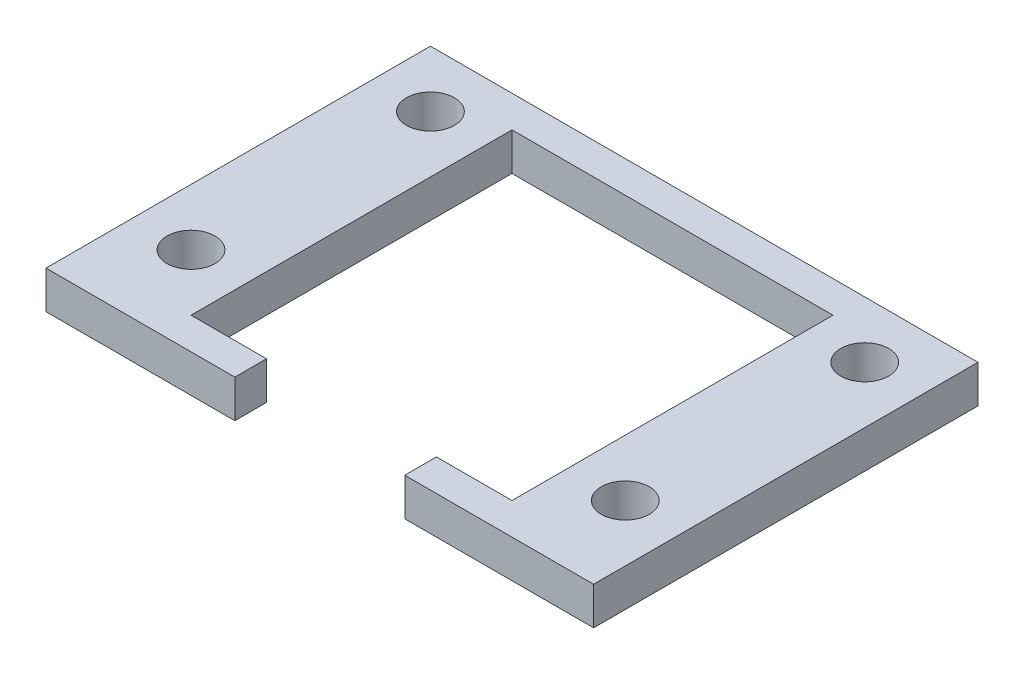
SolidWorks part; units mm, degrees
ref_plane "Front Plane" through (0, 0, 0) normal (0, 0, 1) x (1, 0, 0)
ref_plane "Top Plane" through (0, 0, 0) normal (0, 1, 0) x (1, 0, 0)
ref_plane "Right Plane" through (0, 0, 0) normal (1, 0, 0) x (0, 0, -1)
sketch "Sketch1" plane through (0, 0, 0) normal (0, 1, 0) x (1, 0, 0)
  line L1 (0, 0) -> (42.5, 0)
  line L2 (0, 0) -> (0, 42.5)
  line L3 (0, 42.5) -> (42.5, 42.5)
  line L4 (42.5, 0) -> (42.5, 42.5)
  line L5 (-15, 0) -> (57.5, 0)
  line L6 (-15, 0) -> (-15, 46.7)
  line L7 (-15, 46.7) -> (57.5, 46.7)
  line L8 (57.5, 0) -> (57.5, 46.7)
  line L9 (-15, 0) -> (10, 0)
  line L10 (-15, 0) -> (-15, -4.2)
  line L11 (-15, -4.2) -> (10, -4.2)
  line L12 (10, 0) -> (10, -4.2)
  line L13 (57.5, 0) -> (32.5, 0)
  line L14 (57.5, 0) -> (57.5, -4.2)
  line L15 (57.5, -4.2) -> (32.5, -4.2)
  line L16 (32.5, 0) -> (32.5, -4.2)
  circle A0 centre (-7.5, 7.5) radius 3.175
  circle A1 centre (-7.5, 39.2) radius 3.175
  circle A2 centre (50, 39.2) radius 3.175
  circle A3 centre (50, 7.5) radius 3.175
  dimension "D5" = 6.35
  dimension "D1" = 42.5
  dimension "D2" = 15
  dimension "D3" = 15
  dimension "D4" = 4.2
  dimension "D6" = 7.5
  dimension "D7" = 7.5
  dimension "D8" = 7.5
  dimension "D9" = 7.5
  dimension "D10" = 4.2
  dimension "D11" = 10
extrude "Boss-Extrude1" add sketch "Sketch1" along normal blind 5 contours L5 L8 L7 L6 L2 L3 L4 A3 A2 A1 A0 | L12 L1 L5 L10 L11 | L1 L16 L15 L14 L5 region at (-7.5, 0, -0.8624) region at (-2.5, 0, 2.1) region at (45, 0, 2.1)
